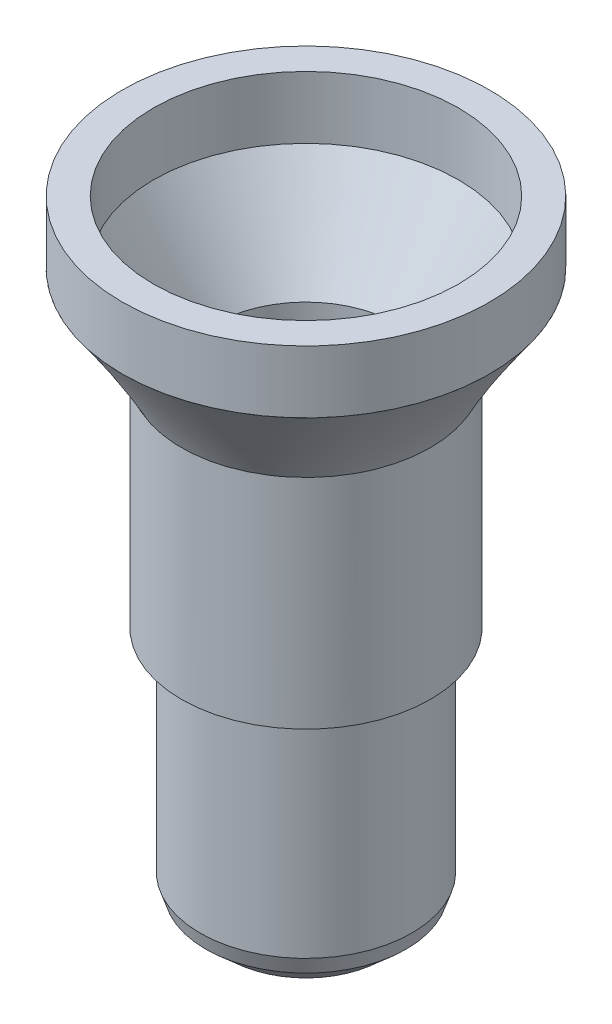
SolidWorks part; units mm, degrees
ref_plane "Alzado" through (0, 0, 0) normal (0, 0, 1) x (1, 0, 0)
ref_plane "Planta" through (0, 0, 0) normal (0, 1, 0) x (1, 0, 0)
ref_plane "Vista lateral" through (0, 0, 0) normal (1, 0, 0) x (0, 0, -1)
sketch "Croquis1" plane through (0, 0, 0) normal (0, 1, 0) x (1, 0, 0)
  circle A0 centre (21.3834, 0) radius 4
  circle A2 centre (21.3834, 0) radius 2.9
  circle A3 centre (21.3834, 0) radius 3.4
  dimension "D1" = 8
  dimension "D2" = 1.1
  dimension "D3" = 0.6
extrude "Saliente-Extruir1" add sketch "Croquis1" along normal blind 12 contours A0 A3 | A3 A2 region at (17.4965, 0, 0) region at (18.0795, 0, 0)
sketch "Croquis3" plane through (0, 12, 0) normal (0, 1, 0) x (1, 0, 0)
  circle A0 centre (21.3834, 0) radius 4.9
  circle A2 centre (21.3834, 0) radius 5.9
  dimension "D2" = 9.8
  dimension "D1" = 1
extrude "Saliente-Extruir2" add sketch "Croquis3" along normal blind 2 from offset 3 contours A2 A0 region at (15.6502, 12, 0)
sketch "Croquis5" plane through (0, 0, 0) normal (0, 0, 1) x (1, 0, 0)
  line L0 (26.8834, 15) -> (25.3834, 12)
  line L1 (17.3834, 12) -> (15.8834, 15)
  line L2 (26.2834, 17) -> (24.2834, 0)
loft "Recubrir4" add section edge at (21.3834, 12, 4) section edge at (21.3834, 15, 5.9) connector at (18.3062, 12, -2.5556) connector at (18.412, 15, -5.0971)
sketch "Croquis6" plane through (0, 0, 0) normal (0, -1, 0) x (1, 0, 0)
  line L1 (21.3834, 0) -> (21.3834, -4) construction
  line L2 (21.3834, 0) -> (17.3834, 0) construction
  line L3 (22.8834, 3.7081) -> (22.8834, 3.5)
  line L5 (19.8834, -3.7081) -> (19.8834, -3.5)
  line L6 (19.8834, -3.5) -> (22.8834, -3.5)
  line L7 (22.8834, -3.7081) -> (22.8834, -3.5)
  line L8 (19.8834, 3.7081) -> (19.8834, 3.5)
  line L9 (19.8834, 3.5) -> (22.8834, 3.5)
  circle A0 centre (21.3834, 0) radius 2
  circle A4 centre (21.3834, 0) radius 3.5
  circle A5 centre (21.3834, 0) radius 4
  point P6 (24.051, 2.2658)
  point P7 (21.3834, 0)
  dimension "D2" = 4
  dimension "D3" = 8
  dimension "D1" = 1.5
ref_plane "Plano2" through (0, -3, 0) normal (0, -1, 0) x (-1, 0, 0)
sketch "Croquis9" plane through (0, -3, 0) normal (0, -1, 0) x (-1, 0, 0)
  circle A0 centre (-21.3834, 0) radius 2
  circle A1 centre (-21.3834, 0) radius 3
loft "Recubrir9" add section "Croquis9" section "Croquis6" connector at (24.3179, -3, 0.6231) connector at (25.1884, 0, 1.2337)
loft "Cortar-Recubrir3" cut section "Croquis9<4>" section "Croquis1<3>" connector at (23.3293, -3, -0.462) connector at (22.5668, 0, -2.6475)
sketch "Croquis9<4>" plane through (0, -3, 0) normal (0, -1, 0) x (-1, 0, 0) same geometry as "Croquis9"
sketch "Croquis1<3>" plane through (0, 0, 0) normal (0, 1, 0) x (1, 0, 0) same geometry as "Croquis1"
loft "Cortar-Recubrir5" cut section edge at (21.3834, 15, 4.9) section edge at (21.3834, 12, 2.9) connector at (25.467, 15, -2.7082) connector at (23.8499, 12, -1.5252)
extrude "Cortar-Extruir2" cut sketch "Croquis1<5>" against normal through all and the other way blind 5 contours A0 | A3
sketch "Croquis1<5>" plane through (0, 0, 0) normal (0, 1, 0) x (1, 0, 0) same geometry as "Croquis1"
chamfer "Chaflán2" distance 0.7 angle 30 1 edges at (21.3834, -3, -3) first distance on face at (21.3834, -1.8, 3.4)
